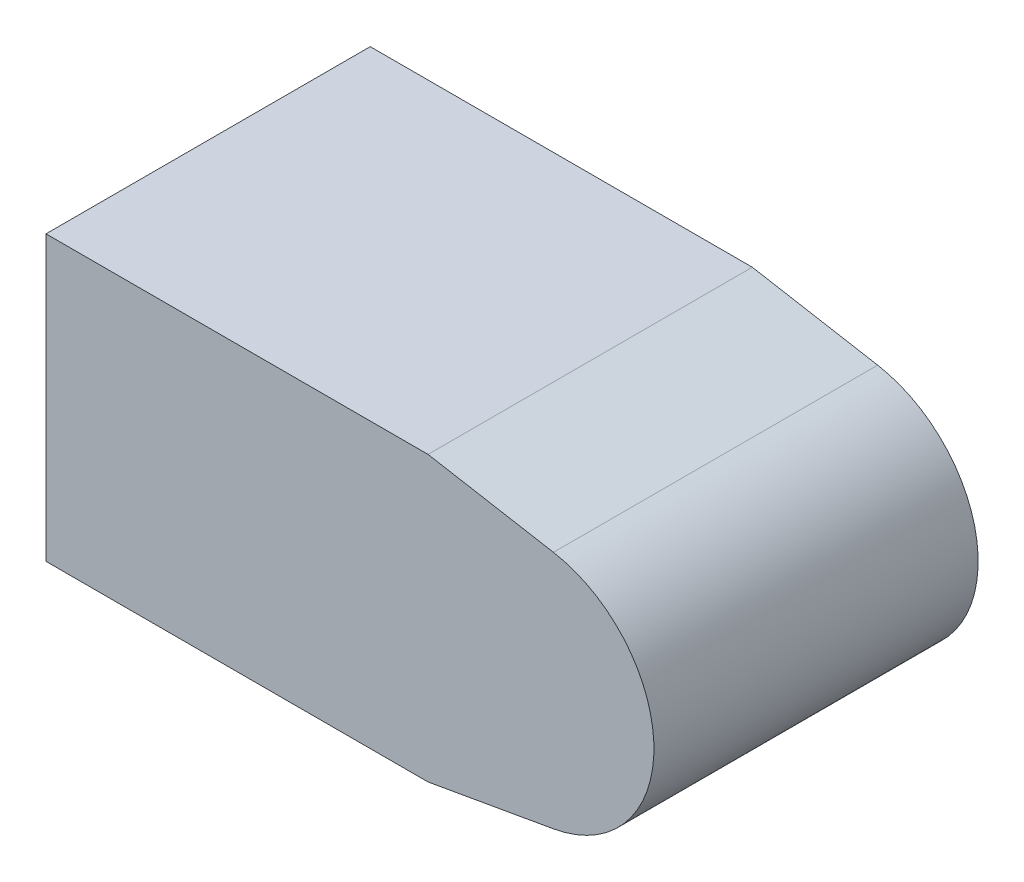
SolidWorks part; units mm, degrees
ref_plane "Front Plane" through (0, 0, 0) normal (0, 0, 1) x (1, 0, 0)
ref_plane "Top Plane" through (0, 0, 0) normal (0, 1, 0) x (1, 0, 0)
ref_plane "Right Plane" through (0, 0, 0) normal (1, 0, 0) x (0, 0, -1)
sketch "Sketch1" plane through (0, 0, 0) normal (0, 0, 1) x (1, 0, 0)
  line L0 (-54.1597, -43.8848) -> (40.1086, -43.8848)
  line L1 (40.1086, -43.8848) -> (71.0498, -38.4291)
  line L2 (71.0498, 20.6594) -> (40.1086, 26.1152)
  line L3 (40.1086, 26.1152) -> (-54.1597, 26.1152)
  line L4 (-54.1597, 26.1152) -> (-54.1597, -43.8848)
  arc A0 (71.0498, -38.4291) -> (71.0498, 20.6594) centre (65.8403, -8.8848) ccw
  dimension "D1" = 170
  dimension "D2" = 170
  dimension "D3" = 70
  dimension "D4" = 120
extrude "Boss-Extrude1" add sketch "Sketch1" along normal mid plane 80
